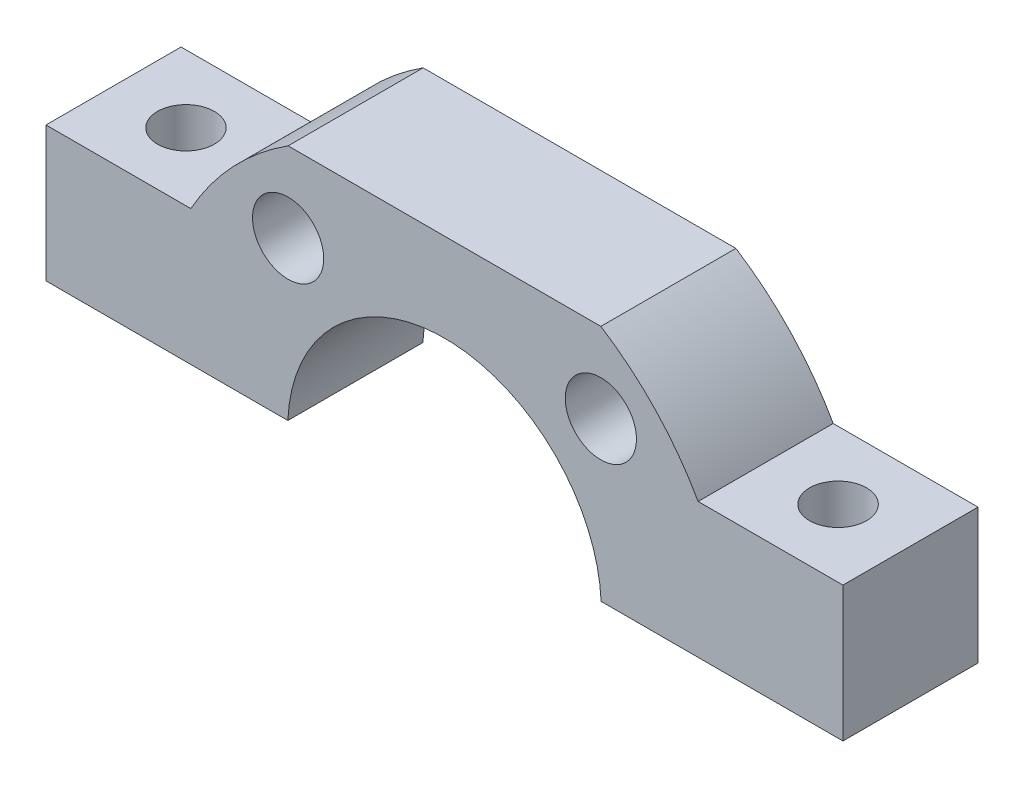
SolidWorks part; units mm, degrees
ref_plane "Front Plane" through (0, 0, 0) normal (0, 0, 1) x (1, 0, 0)
ref_plane "Top Plane" through (0, 0, 0) normal (0, 1, 0) x (1, 0, 0)
ref_plane "Right Plane" through (0, 0, 0) normal (1, 0, 0) x (0, 0, -1)
sketch "Sketch1" plane through (0, 0, 0) normal (0, 0, 1) x (1, 0, 0)
  line L0 (-11.03, 0) -> (-28.03, 0)
  line L1 (-28.03, 0) -> (-28.03, 10)
  line L2 (-28.03, 10) -> (-17.8429, 10)
  line L3 (11.03, 0) -> (28.03, 0)
  line L4 (28.03, 0) -> (28.03, 10)
  line L5 (28.03, 10) -> (17.8429, 10)
  line L6 (-11, 17.2444) -> (11, 17.2444)
  arc A0 (11.03, 0) -> (-11.03, 0) centre (0, 0) ccw
  arc A1 (-17.8429, 10) -> (-11, 17.2444) centre (0, 0) cw
  arc A2 (12.49, 10) -> (-12.49, 10) centre (0, 0) ccw construction
  circle A3 centre (11, 11.619) radius 2.505
  circle A4 centre (-11, 11.619) radius 2.505
  arc A6 (11, 17.2444) -> (17.8429, 10) centre (0, 0) cw
  dimension "D1" = 11.03
  dimension "D6" = 20.4541
  dimension "D7" = 16
  dimension "D8" = 5.01
  dimension "D9" = 5.01
  dimension "D2" = 17
  dimension "D3" = 17
  dimension "D4" = 10
  dimension "D5" = 10
extrude "Boss-Extrude2" add sketch "Sketch1" along normal blind 9.5
sketch "Sketch2" plane through (0, 10, 0) normal (0, 1, 0) x (1, 0, 0)
  line L0 (28.03, -9.5) -> (28.03, 0) construction
  line L1 (-28.03, -4.75) -> (28.03, -4.75) construction
  line L2 (-28.03, -9.5) -> (-28.03, 0) construction
  line L3 (-22.9364, 0) -> (-22.9364, -9.5) construction
  line L4 (-17.8429, 0) -> (-28.03, 0) construction
  line L5 (-17.8429, -9.5) -> (-28.03, -9.5) construction
  line L6 (22.9364, 0) -> (22.9364, -9.5) construction
  line L7 (28.03, 0) -> (17.8429, 0) construction
  line L8 (28.03, -9.5) -> (17.8429, -9.5) construction
  circle A0 centre (22.9364, -4.75) radius 2.005
  circle A1 centre (-22.9364, -4.75) radius 2
  dimension "D1" = 4.01
  dimension "D2" = 4
extrude "Cut-Extrude1" cut sketch "Sketch2" against normal up to next
sketch "Sketch3" plane through (0, 0, 0) normal (0, -1, 0) x (1, 0, 0)
  line L1 (-35.1968, 10.8816) -> (37.799, 10.8816)
  line L2 (-35.1968, 10.8816) -> (-35.1968, -7.2673)
  line L3 (-35.1968, -7.2673) -> (37.799, -7.2673)
  line L4 (37.799, 10.8816) -> (37.799, -7.2673)
extrude "Cut-Extrude2" cut sketch "Sketch3" against normal blind 0.5
